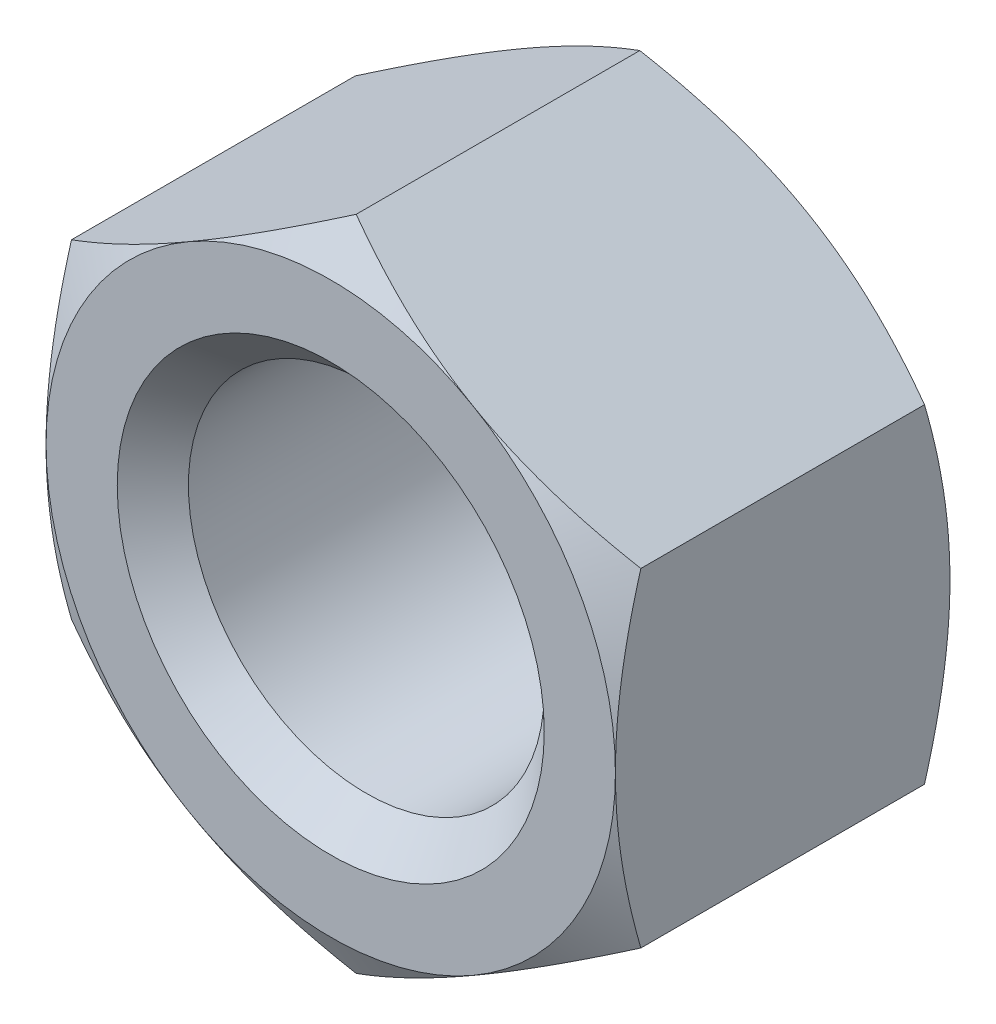
SolidWorks part; units mm, degrees
ref_plane "Front Plane" through (0, 0, 0) normal (0, 0, 1) x (1, 0, 0)
ref_plane "Top Plane" through (0, 0, 0) normal (0, 1, 0) x (1, 0, 0)
ref_plane "Right Plane" through (0, 0, 0) normal (1, 0, 0) x (0, 0, -1)
sketch "Sketch1" plane through (0, 0, 0) normal (0, 0, 1) x (1, 0, 0)
  line L1 (0, 4.6188) -> (-4, 2.3094)
  line L2 (-4, 2.3094) -> (-4, -2.3094)
  line L3 (-4, -2.3094) -> (0, -4.6188)
  line L4 (0, -4.6188) -> (4, -2.3094)
  line L5 (4, -2.3094) -> (4, 2.3094)
  line L6 (4, 2.3094) -> (0, 4.6188)
  circle A0 centre (0, 0) radius 4 construction
  circle A1 centre (0, 0) radius 2.5
  circle A3 centre (0, 0) radius 5
  dimension "D1" = 10
  dimension "D2" = 8
extrude "Boss-Extrude1" add sketch "Sketch1" along normal blind 4.7 contours A3 L6 L5 L4 L3 L2 L1 | L5 L6 L1 L2 L3 L4 A1 region at (1.9389, 3.3583, 0) region at (-4.8586, 0, 0)
chamfer "Chamfer1" distance 1 angle 30 1 edges at (5, 0, 4.7) first distance on face at (5, 0, 4.7)
chamfer "Chamfer2" distance 1 angle 30 1 edges at (5, 0, 0) first distance on face at (5, 0, 0)
extrude "Cut-Extrude1" cut sketch "Sketch1<3>" along normal through all contours A3 L6 L5 L4 L3 L2 L1 region at (-4.8586, 0, 0)
sketch "Sketch1<3>" plane through (0, 0, 0) normal (0, 0, 1) x (1, 0, 0) same geometry as "Sketch1"
chamfer "Chamfer3" distance 0.5 angle 45 2 edges at (2.5, 0, 0) (2.5, 0, 4.7)
